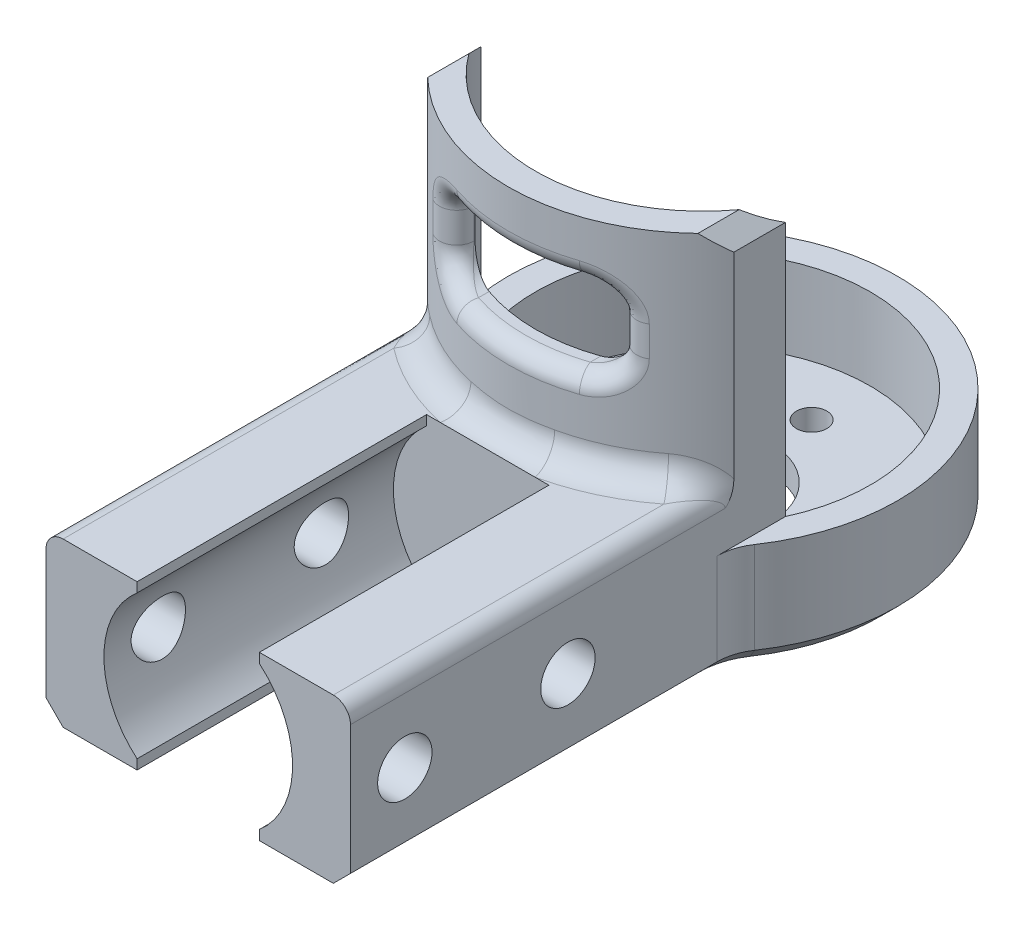
SolidWorks part; units mm, degrees
ref_plane "Front Plane" through (0, 0, 0) normal (0, 0, 1) x (1, 0, 0)
ref_plane "Top Plane" through (0, 0, 0) normal (0, 1, 0) x (1, 0, 0)
ref_plane "Right Plane" through (0, 0, 0) normal (1, 0, 0) x (0, 0, -1)
sketch "Sketch1" plane through (0, 0, 0) normal (0, 1, 0) x (1, 0, 0)
  line L0 (17.78, -25.4) -> (-17.78, 25.5194) construction
  line L1 (17.78, -25.4) -> (-17.78, -25.4)
  line L2 (17.78, -25.4) -> (17.78, 25.4)
  line L4 (-17.78, -25.4) -> (-17.78, 25.4)
  line L6 (17.78, 25.4) -> (-17.78, -25.4) construction
  circle A0 centre (0, 33.5382) radius 19.554
  circle A1 centre (0, 33.5382) radius 22.729
  circle A2 centre (0, 33.5382) radius 7.9629
  circle A3 centre (0, 46.2382) radius 1.778
  circle A4 centre (12.7, 33.5382) radius 1.778
  circle A5 centre (0, 20.8382) radius 1.778
  circle A6 centre (-12.7, 33.5382) radius 1.778
  point P22 (0, 33.5382)
  dimension "D2" = 39.108
  dimension "D5" = 4
  dimension "D3" = 12.7
  dimension "D6" = 15.9258
  dimension "D7" = 50.8
  dimension "D1" = 35.56
  dimension "D8" = 50.8
  dimension "D4" = 3.175
extrude "Boss-Extrude1" add sketch "Sketch1" along normal blind 12.7 contours L2 A1 L4 A0 region at (18.3654, 0, -22.3896)
extrude "Boss-Extrude2" add sketch "Sketch1<3>" along normal blind 44.45 contours L4 A1 L2 A0 region at (0, 0, -11.1936)
sketch "Sketch1<3>" plane through (0, 0, 0) normal (0, 1, 0) x (1, 0, 0) same geometry as "Sketch1"
extrude "Boss-Extrude3" add sketch "Sketch1<5>" along normal blind 19.05 contours A1 L4 L1 L2 region at (0, 0, 5.918)
sketch "Sketch1<5>" plane through (0, 0, 0) normal (0, 1, 0) x (1, 0, 0) same geometry as "Sketch1"
extrude "Boss-Extrude4" add sketch "Sketch1<6>" along normal blind 3.175 contours A0 A6 A5 A4 A3 A2 region at (0, 0, -14.5373)
sketch "Sketch1<6>" plane through (0, 0, 0) normal (0, 1, 0) x (1, 0, 0) same geometry as "Sketch1"
sketch "Sketch2" plane through (0, 0, 25.4) normal (0, 0, 1) x (1, 0, 0)
  line L0 (-17.78, 9.525) -> (17.78, 9.525) construction
  line L1 (-17.78, 19.05) -> (-17.78, 0) construction
  line L2 (17.78, 19.05) -> (17.78, 0) construction
  line L3 (17.78, 19.05) -> (-17.78, 19.05) construction
  line L4 (7.1437, 0) -> (-7.1438, 0)
  line L5 (7.1437, 0) -> (7.1437, 1.1367)
  line L6 (7.1437, 19.05) -> (-7.1438, 19.05)
  line L7 (-7.1438, 0) -> (-7.1438, 1.1367)
  line L8 (7.1437, 0) -> (-7.1438, 19.05) construction
  line L9 (7.1437, 19.05) -> (-7.1438, 0) construction
  line L10 (-7.1438, 17.9133) -> (-7.1438, 19.05)
  line L11 (7.1437, 17.9133) -> (7.1437, 19.05)
  arc A0 (-7.1438, 17.9133) -> (-7.1438, 1.1367) centre (0, 9.525) ccw
  arc A1 (5.5381, 19.05) -> (-5.5381, 19.05) centre (0, 9.525) ccw
  arc A2 (-5.5381, 0) -> (5.5381, 0) centre (0, 9.525) ccw
  arc A3 (7.1437, 1.1367) -> (7.1437, 17.9133) centre (0, 9.525) ccw
  line M1 (-17.78, 0) -> (17.78, 0)
  line M3 (17.78, 19.05) -> (-17.78, 19.05)
  dimension "D1" = 22.036
  dimension "D2" = 14.2875
extrude "Cut-Extrude1" cut sketch "Sketch2" against normal blind 33.8125 contours L5 A3 L11 L6 L10 A0 L7 L4 M3 M1 region at (0, 9.525, 25.4)
sketch "Sketch3" plane through (17.78, 0, 0) normal (1, 0, 0) x (0, 0, -1)
  line L0 (-25.4, 9.525) -> (19.3792, 9.525) construction
  line L1 (-25.4, 19.05) -> (-25.4, 0) construction
  line L2 (19.3792, 12.7) -> (19.3792, 0) construction
  circle A0 centre (-19.05, 9.525) radius 3.175
  circle A1 centre (0, 9.525) radius 3.175
  dimension "D1" = 2
  dimension "D2" = 6.35
extrude "Cut-Extrude2" cut sketch "Sketch3" against normal through all
fillet "Fillet1" radius 6 2 edges at (17.78, 6.35, -19.3792) (-17.78, 6.35, -19.3792)
chamfer "Chamfer3" distance 2 angle 45 2 edges at (17.78, 44.45, -22.3896) (-17.78, 44.45, -22.3896)
fillet "Fillet8" radius 2 2 edges at (-17.78, 19.05, 3.0104) (17.78, 19.05, 3.0104)
chamfer "Chamfer6" distance 2 angle 45 5 edges at (-17.78, 0, 3.9911) (-18.0442, 0, -19.1787) (0, 0, -56.2672) (18.0442, 0, -19.1787) (17.78, 0, 3.9911)
fillet "Fillet13" radius 3 3 edges at (-17.5556, 17.9705, -19.1018) (17.2989, 18.3512, -18.7952) (0, 19.05, -10.8092)
sketch "Sketch4" plane through (0, 0, 0) normal (0, 0, 1) x (1, 0, 0)
  line L0 (0, 21.9887) -> (0, 44.45) construction
  line L1 (15.78, 44.45) -> (-15.78, 44.45) construction
  line L3 (9.525, 28.4569) -> (-9.525, 28.4569)
  line L4 (9.525, 28.4569) -> (9.525, 37.9819)
  line L5 (9.525, 37.9819) -> (-9.525, 37.9819)
  line L6 (-9.525, 28.4569) -> (-9.525, 37.9819)
  line L7 (9.525, 28.4569) -> (-9.525, 37.9819) construction
  line L8 (9.525, 37.9819) -> (-9.525, 28.4569) construction
  spline S0 degree 3 poles (-4.8931, 22.05) (-4.0867, 22.05) (-3.2747, 22.031) (-1.6391, 22.0003) (-0.8123, 21.9886) (0.8313, 21.9888) (1.6491, 22.0005) (3.2769, 22.0311) (4.0869, 22.05) (4.8931, 22.05) knots 0 0 0 0 0.25 0.25 0.5 0.5 0.75 0.75 1 1 1 1 construction
  point P6 (0, 33.2194)
  dimension "D1" = 9.525
  dimension "D2" = 19.05
extrude "Cut-Extrude3" cut sketch "Sketch4" against normal blind 44.45
fillet "Fillet14" radius 3 4 edges at (9.525, 37.9819, -14.6811) (9.525, 28.4569, -14.6811) (-9.525, 37.9819, -14.6811) (-9.525, 28.4569, -14.6811)
fillet "Fillet15" radius 2 8 edges at (8.9575, 29.701, -12.6487) (9.525, 33.2194, -12.9013) (8.4734, 37.263, -12.4477) (0, 37.9819, -10.8092) (-8.9575, 36.7377, -12.6487) (-9.525, 33.2194, -12.9013) (-8.4734, 29.1757, -12.4477) (0, 28.4569, -10.8092)
